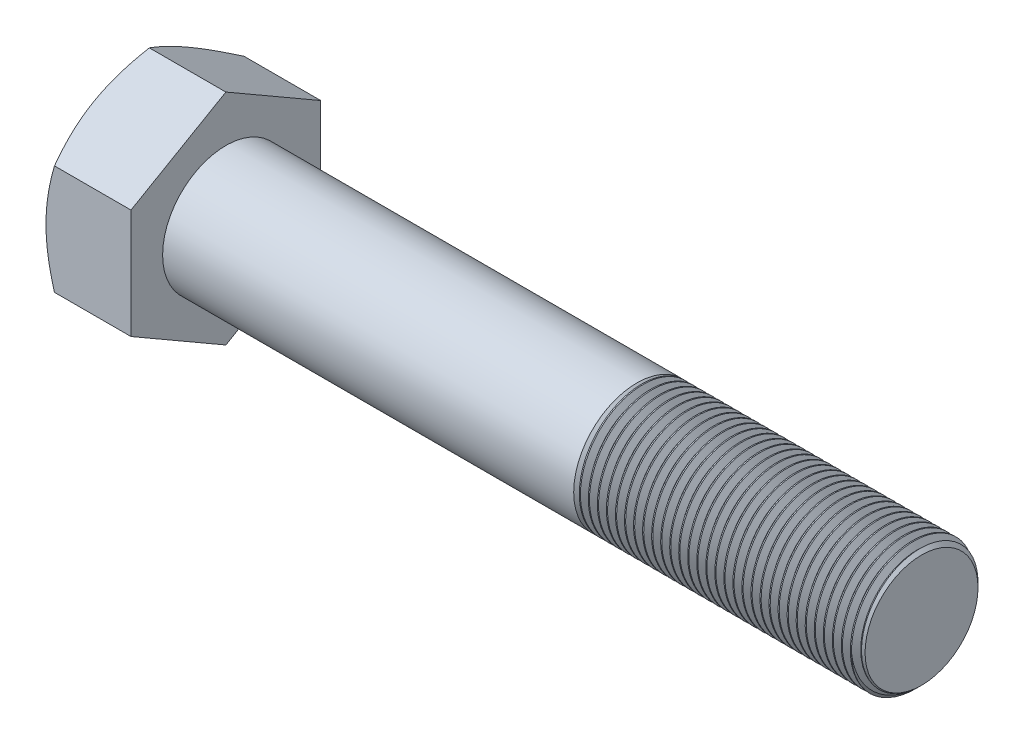
SolidWorks part; units mm, degrees
material "Galvanized Steel"
ref_plane "Front Plane" through (0, 0, 0) normal (0, 0, 1) x (1, 0, 0)
ref_plane "Top Plane" through (0, 0, 0) normal (0, 1, 0) x (1, 0, 0)
ref_plane "Right Plane" through (0, 0, 0) normal (1, 0, 0) x (0, 0, -1)
sketch "Sketch1" plane through (0, 0, 0) normal (0, 0, 1) x (1, 0, 0)
  line L0 (-78.3828, 0) -> (78.3828, 0) construction
  line L1 (78.3828, 12.7) -> (78.3828, -12.7) construction
  line L2 (-61.3172, 19.05) -> (-61.3172, -19.05) construction
  line L3 (-78.3828, 19.05) -> (-78.3828, -19.05) construction
  point P9 (-61.3172, 0)
  point P10 (72.0328, -12.7)
  dimension "Screw Dia" = 25.4
  dimension "Hex" = 38.1
  dimension "Head Ht" = 17.0656
  dimension "Screw Lenght" = 139.7
  dimension "D1" = 6.35
ref_plane "Plane2" through (78.3828, 0, 0) normal (1, 0, 0) x (0, 0, -1)
sketch "Sketch5" plane through (78.3828, 0, 0) normal (1, 0, 0) x (0, 0, -1)
  circle A0 centre (0, 0) radius 12.7
extrude "Boss-Extrude3" add sketch "Sketch5" against normal up to vertex (139.7 mm away) up to point (-61.3172, 0, 0)
sketch "Sketch9" plane through (78.3828, 0, 0) normal (1, 0, 0) x (0, 0, -1)
  circle A1 centre (0, 0) radius 12.7
  circle A2 centre (0, 0) radius 12.7
  dimension "D1" = 0
curve "Helix/Spiral1" pitch 1.8143 height 58.9643 turns 32.5 parameters "Pitch"=1.8143
chamfer "Chamfer1" distance 1.3607 angle 45 1 edges at (78.3828, 0, -12.7)
sketch "Sketch10" plane through (0, 0, 0) normal (0, 0, 1) x (1, 0, 0)
  line L0 (78.3828, 12.7) -> (79.0632, 11.5216)
  line L1 (79.0632, 11.5216) -> (79.29, 11.5216)
  line L2 (79.29, 11.5216) -> (79.9703, 12.7)
  line L3 (78.3828, 12.7) -> (79.9703, 12.7)
  line L4 (79.1766, 12.7) -> (79.1766, 11.5216) construction
  line L5 (78.723, 12.1108) -> (79.6301, 12.1108) construction
  dimension "D1" = 60
  dimension "D2" = 0.2268
  dimension "D3" = 0.9071
sweep "Cut-Sweep1" cut profiles "Sketch10" path "Helix/Spiral1" align with end faces yes
sketch "Sketch11" plane through (0, 0, 0) normal (0, 0, 1) x (1, 0, 0)
  line L0 (-61.3172, 12.7) -> (-61.3172, 0)
  line L1 (-61.3172, 0) -> (33.9328, 0)
  line L3 (33.9328, 0) -> (21.2328, 12.7)
  line L4 (-61.3172, 12.7) -> (21.2328, 12.7)
  dimension "D1" = 45
  dimension "MIn Thread" = 57.15
revolve "Revolve1" add sketch "Sketch11" angle 360 about L1
sketch "Sketch6" plane through (-61.3172, 0, 0) normal (-1, 0, 0) x (0, 0, 1)
  line L0 (0, 19.05) -> (0, -19.05) construction
  line L1 (19.05, 10.9985) -> (0, 21.997)
  line L2 (0, 21.997) -> (-19.05, 10.9985)
  line L3 (-19.05, 10.9985) -> (-19.05, -10.9985)
  line L4 (-19.05, -10.9985) -> (0, -21.997)
  line L5 (0, -21.997) -> (19.05, -10.9985)
  line L6 (19.05, -10.9985) -> (19.05, 10.9985)
  circle A0 centre (0, 0) radius 19.05 construction
extrude "Boss-Extrude4" add sketch "Sketch6" along normal up to vertex (17.0656 mm away) up to point (-78.3828, -19.05, 0)
sketch "Sketch7" plane through (-78.3828, 0, 0) normal (-1, 0, 0) x (0, 0, 1)
  circle A0 centre (0, 0) radius 19.05 construction
  circle A1 centre (0, 0) radius 19.05
sketch "Sketch8" plane through (-78.3828, 0, 0) normal (-1, 0, 0) x (0, 0, 1)
  circle A0 centre (0, 0) radius 19.05 construction
  circle A1 centre (0, 0) radius 19.05
extrude "Cut-Extrude3" cut sketch "Sketch8" against normal through all draft 60 flip side to cut
sketch "Sketch12" plane through (-78.3828, 0, 0) normal (-1, 0, 0) x (0, 0, 1)
  line L0 (0, 14.6685) -> (0, 8.1915) construction
  line L1 (0.5715, 14.6685) -> (0.5715, 8.1915)
  line L2 (-0.5715, 14.6685) -> (-0.5715, 8.1915)
  line L3 (0, 12.7) -> (0, -12.7) construction
  arc A0 (0.5715, 14.6685) -> (-0.5715, 14.6685) centre (0, 14.6685) ccw
  arc A1 (-0.5715, 8.1915) -> (0.5715, 8.1915) centre (0, 8.1915) ccw
  circle A3 centre (0, 0) radius 7.62 construction
  circle A4 centre (0, 0) radius 15.24 construction
  point P2 (0, 11.43)
  dimension "D1" = 15.24
  dimension "D3" = 30.48
  dimension "D2" = 1.143
extrude "Cut-Extrude4" cut sketch "Sketch12" against normal blind 0.254
pattern_circular "CirPattern1" count 3 over 360 about axis through (0, 0, 0) along (1, 0, 0) of "Cut-Extrude4"
equation "\"D2@Sketch10\" = \"Pitch@Helix/Spiral1\"*.125"
equation "\"D3@Sketch10\" = \"Pitch@Helix/Spiral1\"*.5"
equation "\"D3@Helix/Spiral1\" = \"MIn Thread@Sketch11\"+\"Pitch@Helix/Spiral1\""
equation "\"D1@Chamfer1\" = \"Pitch@Helix/Spiral1\"*.75"
equation "\"D1@Sketch12\" = \"Hex@Sketch1\"*.4"
equation "\"D3@Sketch12\" = \"Hex@Sketch1\"*.8"
equation "\"D2@Sketch12\" = \"Hex@Sketch1\"*.03"
equation "\"D1@Sketch1\" = \"Pitch@Helix/Spiral1\"*3.5"
